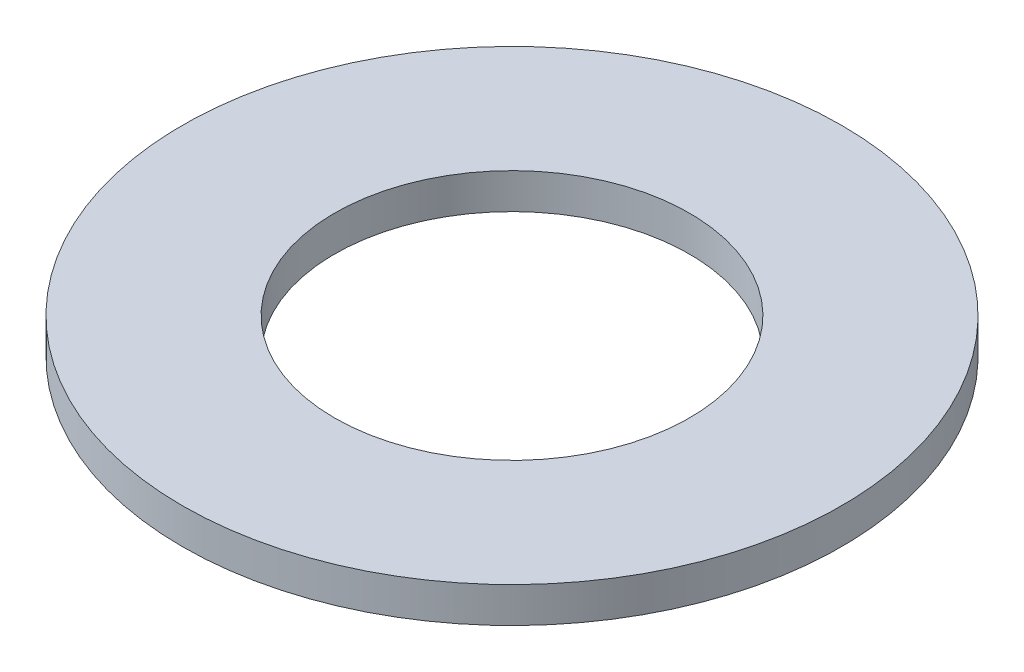
SolidWorks part; units mm, degrees
ref_plane "Front Plane" through (0, 0, 0) normal (0, 0, 1) x (1, 0, 0)
ref_plane "Top Plane" through (0, 0, 0) normal (0, 1, 0) x (1, 0, 0)
ref_plane "Right Plane" through (0, 0, 0) normal (1, 0, 0) x (0, 0, -1)
sketch "Sketch1" plane through (0, 0, 0) normal (0, 1, 0) x (1, 0, 0)
  circle A0 centre (0, 0) radius 65
  dimension "FLANGE_OD" = 130
extrude "Boss-Extrude1" add sketch "Sketch1" along normal blind 7
sketch "Sketch2" plane through (0, 0, 0) normal (0, 1, 0) x (1, 0, 0)
  circle A0 centre (0, 0) radius 35
  dimension "BORE_D" = 70
extrude "Cut-Extrude1" cut sketch "Sketch2" along normal through all
sketch "Sketch3" plane through (0, 7, 0) normal (0, 1, 0) x (1, 0, 0)
  circle A0 centre (0, 0) radius 26.3594 construction
  circle A1 centre (-26.3594, 0) radius 2.9992
  dimension "BOLT_D" = 5.9984
  dimension "BOLT_PCD" = 52.7188
extrude "Cut-Extrude2" cut sketch "Sketch3" against normal blind 5.9567 rebuild error yes
pattern_circular "CirPattern1" count 6 over 360 rebuild error yes
